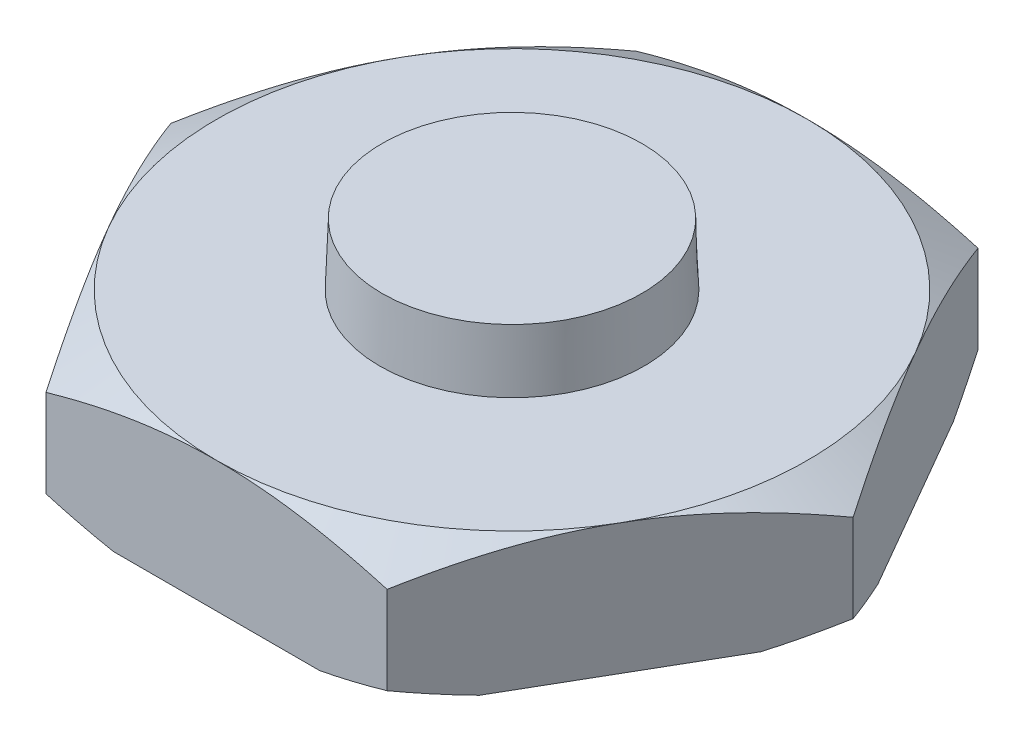
SolidWorks part; units mm, degrees
ref_plane "Front Plane" through (0, 0, 0) normal (0, 0, 1) x (1, 0, 0)
ref_plane "Top Plane" through (0, 0, 0) normal (0, 1, 0) x (1, 0, 0)
ref_plane "Right Plane" through (0, 0, 0) normal (1, 0, 0) x (0, 0, -1)
ref_plane "Plane1" through (0, 0, 0) normal (0, 0, 1) x (1, 0, 0)
sketch "Sketch1" plane through (0, 0, 0) normal (0, 0, 1) x (1, 0, 0)
  line L0 (0, 34.0386) -> (5.5795, 34.0386)
  line L1 (5.5795, 34.0386) -> (5.5795, 14.2396)
  line L2 (5.5795, 14.2396) -> (5.6822, 11.4036)
  line L3 (5.6822, 11.4036) -> (12.7, 11.4036)
  line L4 (12.7, 11.4036) -> (17.9334, 8.3821)
  line L5 (17.9334, 8.3821) -> (13.45, 5.7936)
  line L6 (13.45, 5.7936) -> (0, 5.7936)
  line L7 (0, 5.7936) -> (0, 34.0386)
  line L8 (0, 5.7936) -> (0, 34.0386) construction
revolve "Revolve1" add sketch "Sketch1" angle 360 about L8 reverse direction yes
ref_plane "Plane2" through (0, 11.4036, 0) normal (0, 1, 0) x (1, 0, 0)
sketch "Sketch2" plane through (0, 11.4036, 0) normal (0, 1, 0) x (1, 0, 0)
  line L0 (23.734, -20.3506) -> (23.734, 18.7347)
  line L1 (23.734, 18.7347) -> (-23.431, 18.7347)
  line L2 (-23.431, 18.7347) -> (-23.431, -20.3506)
  line L3 (-23.431, -20.3506) -> (23.734, -20.3506)
  line L4 (14.6647, 0) -> (7.3323, 12.7)
  line L5 (7.3323, 12.7) -> (-7.3323, 12.7)
  line L6 (-7.3323, 12.7) -> (-14.6647, 0)
  line L7 (-14.6647, 0) -> (-7.3323, -12.7)
  line L8 (-7.3323, -12.7) -> (7.3323, -12.7)
  line L9 (7.3323, -12.7) -> (14.6647, 0)
extrude "Cut-Extrude1" cut sketch "Sketch2" against normal blind 5.61
ref_plane "Plane3" through (0, 14.0616, 0) normal (0, 1, 0) x (1, 0, 0)
sketch "Sketch3" plane through (0, 14.0616, 0) normal (0, 1, 0) x (1, 0, 0)
  line L0 (-20, -20) -> (20, -20)
  line L1 (20, -20) -> (20, 20)
  line L2 (20, 20) -> (-20, 20)
  line L3 (-20, 20) -> (-20, -20)
extrude "Cut-Extrude2" cut sketch "Sketch3" along normal blind 50
